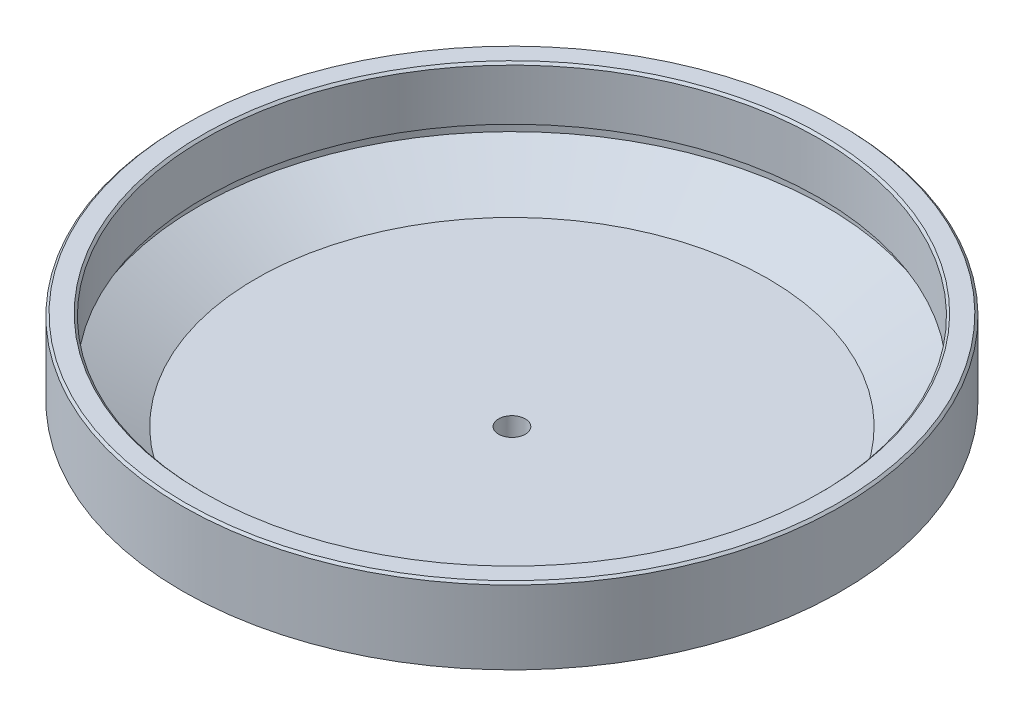
SolidWorks part; units mm, degrees
material "AISI 304"
ref_plane "Спереди" through (0, 0, 0) normal (0, 0, 1) x (1, 0, 0)
ref_plane "Сверху" through (0, 0, 0) normal (0, 1, 0) x (1, 0, 0)
ref_plane "Справа" through (0, 0, 0) normal (1, 0, 0) x (0, 0, -1)
ref_axis "ОсьX" through (-88.99, 0, 0) along (1, 0, 0)
ref_axis "ОсьZ" through (0, 55, 0) along (0, -1, 0)
ref_axis "ОсьY" through (0, 0, -88.99) along (0, 0, 1)
sketch "Эскиз1" plane through (0, 0, 0) normal (0, 0, 1) x (1, 0, 0)
  line L0 (-74, 28) -> (-74, 11)
  line L1 (0, 26.169) -> (0, -22.1581) construction
  line L2 (-54.9474, 0) -> (-3, 0)
  line L3 (-3, 0) -> (-3, 6)
  line L4 (-3, 6) -> (-57.5096, 6)
  line L5 (-70.5, 13.5) -> (-70.5, 16)
  line L6 (-70.5, 16) -> (-69, 16)
  line L7 (-69, 16) -> (-69, 28)
  line L8 (-69, 28) -> (-74, 28)
  line L11 (-74, 11) -> (-54.9474, 0)
  line L12 (-70.5, 13.5) -> (-57.5096, 6)
  dimension "D1" = 148
  dimension "D2" = 60
  dimension "D3" = 138
  dimension "D4" = 6
  dimension "D5" = 6
  dimension "D6" = 17
  dimension "D7" = 1.5
  dimension "D8" = 2.5
  dimension "D9" = 12
  dimension "D10" = 28
revolve "Повернуть1" add sketch "Эскиз1" angle 360 mid plane about L1
cosmetic thread "Условное изображение резьбы2" parameters "D2"=8
chamfer "Фаска1" distance 0.5 angle 45 3 edges at (0, 0, 3) (0, 28, 74) (0, 28, 69)
